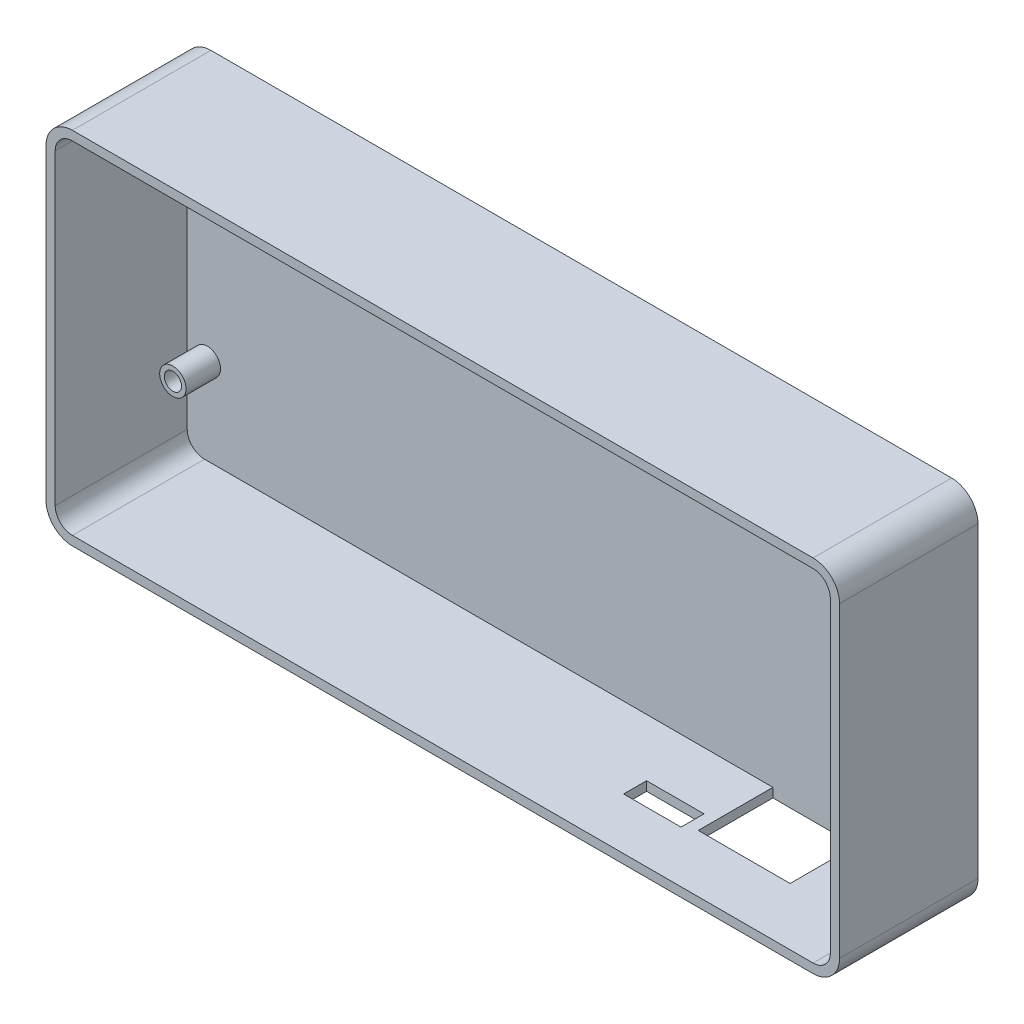
SolidWorks part; units mm, degrees
ref_plane "Alzado" through (0, 0, 0) normal (0, 0, 1) x (1, 0, 0)
ref_plane "Planta" through (0, 0, 0) normal (0, 1, 0) x (1, 0, 0)
ref_plane "Vista lateral" through (0, 0, 0) normal (1, 0, 0) x (0, 0, -1)
sketch "Croquis1" plane through (0, 0, 0) normal (0, 0, 1) x (1, 0, 0)
  line L0 (3, 61.1) -> (132, 61.1)
  line L1 (3, 0) -> (132, 0)
  line L2 (0, 3) -> (0, 56.5)
  line L3 (3, 59.5) -> (132, 59.5)
  line L4 (135, 3) -> (135, 56.5)
  line L5 (136.6, 3) -> (136.6, 56.5)
  line L6 (3, -1.6) -> (132, -1.6)
  line L7 (-1.6, 3) -> (-1.6, 56.5)
  arc A0 (132, 59.5) -> (135, 56.5) centre (132, 56.5) cw
  arc A1 (132, 0) -> (135, 3) centre (132, 3) ccw
  arc A2 (3, 0) -> (0, 3) centre (3, 3) cw
  arc A3 (0, 56.5) -> (3, 59.5) centre (3, 56.5) cw
  arc A4 (132, 61.1) -> (136.6, 56.5) centre (132, 56.5) cw
  arc A5 (132, -1.6) -> (136.6, 3) centre (132, 3) ccw
  arc A6 (3, -1.6) -> (-1.6, 3) centre (3, 3) cw
  arc A7 (-1.6, 56.5) -> (3, 61.1) centre (3, 56.5) cw
  point P9 (135, 0)
  point P12 (0, 0)
  point P15 (0, 59.5)
  dimension "D3" = 3
  dimension "D1" = 135
  dimension "D2" = 59.5
  dimension "D4" = 1.6
extrude "pared" add sketch "Croquis1" along normal blind 23
sketch "Croquis2" plane through (0, -1.6, 0) normal (0, -1, 0) x (1, 0, 0)
  line L0 (0, 23) -> (0, 0) construction
  line L1 (135, 23) -> (135, 0) construction
  line L2 (3, 23) -> (-1.6, 23) construction
  line L3 (-1.6, 23) -> (-1.6, 0) construction
  line L4 (-1.6, 0) -> (3, 0) construction
  line L5 (3, 0) -> (132, 0) construction
  line L6 (132, 0) -> (136.6, 0) construction
  line L7 (136.6, 23) -> (136.6, 0) construction
  line L8 (136.6, 23) -> (132, 23) construction
  line L9 (3, 23) -> (132, 23) construction
  line L10 (0, 23) -> (0, 0)
  line L11 (135, 23) -> (135, 0)
  line L12 (3, 23) -> (-1.6, 23)
  line L13 (-1.6, 23) -> (-1.6, 0)
  line L14 (-1.6, 0) -> (3, 0)
  line L15 (3, 0) -> (132, 0)
  line L16 (132, 0) -> (136.6, 0)
  line L17 (136.6, 23) -> (136.6, 0)
  line L18 (136.6, 23) -> (132, 23)
  line L19 (3, 23) -> (132, 23)
  line L21 (102, 13) -> (118, 13)
  line L22 (102, 13) -> (102, 0)
  line L23 (102, 0) -> (118, 0)
  line L24 (118, 13) -> (118, 0)
  line L25 (90, 14) -> (100, 14)
  line L26 (90, 14) -> (90, 10)
  line L27 (90, 10) -> (100, 10)
  line L28 (100, 14) -> (100, 10)
  dimension "D1" = 0
  dimension "D2" = 13
  dimension "D3" = 17
  dimension "D4" = 16
  dimension "D5" = 10
  dimension "D6" = 4
  dimension "D7" = 35
  dimension "D8" = 10
extrude "conectores" cut sketch "Croquis2" against normal up to next contours L24 L21 L22 L23 | L28 L25 L26 L27 region at (110, -1.6, 6.5) region at (95, -1.6, 12)
extrude "base frente" add sketch "Croquis1<2>" against normal blind 1.12 contours A6 L7 A7 L0 A4 L5 A5 L6
sketch "Croquis1<2>" plane through (0, 0, 0) normal (0, 0, 1) x (1, 0, 0) same geometry as "Croquis1"
sketch "Croquis3" plane through (0, 0, 0) normal (0, 0, 1) x (1, 0, 0)
  line L4 (135, 3) -> (135, 56.5)
  line L5 (132, 59.5) -> (3, 59.5)
  line L6 (0, 56.5) -> (0, 3)
  line L7 (3, 0) -> (102, 0)
  line L8 (135, 3) -> (135, 56.5)
  line L9 (132, 59.5) -> (3, 59.5)
  line L10 (0, 56.5) -> (0, 3)
  line L11 (3, 0) -> (102, 0)
  line L24 (130.5, 48) -> (130.5, 41.5) construction
  line L25 (130.5, 28.5) -> (130.5, 17.5) construction
  line L32 (102, 0) -> (102, -1.6)
  line L33 (102, 0) -> (102, -1.6)
  line L34 (102, -1.6) -> (118, -1.6)
  line L35 (102, -1.6) -> (118, -1.6)
  line L36 (118, -1.6) -> (118, 0)
  line L37 (118, -1.6) -> (118, 0)
  line L38 (118, 0) -> (132, 0)
  line L39 (118, 0) -> (132, 0)
  arc A4 (132, 0) -> (135, 3) centre (132, 3) ccw
  arc A5 (135, 56.5) -> (132, 59.5) centre (132, 56.5) ccw
  arc A6 (3, 59.5) -> (0, 56.5) centre (3, 56.5) ccw
  arc A7 (0, 3) -> (3, 0) centre (3, 3) ccw
  arc A8 (132, 0) -> (135, 3) centre (132, 3) ccw
  arc A9 (135, 56.5) -> (132, 59.5) centre (132, 56.5) ccw
  arc A10 (3, 59.5) -> (0, 56.5) centre (3, 56.5) ccw
  arc A11 (0, 3) -> (3, 0) centre (3, 3) ccw
  circle A16 centre (130.5, 48) radius 1.5
  circle A17 centre (130.5, 41.5) radius 1.5
  circle A18 centre (130.5, 35) radius 1.5
  circle A19 centre (130.5, 28.5) radius 1.5
  circle A20 centre (130.5, 17.5) radius 1.5
  circle A21 centre (130.5, 11.5) radius 2.5
  circle A22 centre (130.5, 48) radius 2.3
  circle A23 centre (130.5, 41.5) radius 2.3
  circle A24 centre (130.5, 35) radius 2.3
  circle A25 centre (130.5, 28.5) radius 2.3
  circle A26 centre (130.5, 17.5) radius 2.3
  circle A27 centre (130.5, 11.5) radius 3.3
  circle A28 centre (3.5, 15) radius 1.5
  circle A29 centre (3.5, 15) radius 2.3
  dimension "D8" = 0.8
  dimension "D14" = 3
  dimension "D3" = 5
  dimension "D6" = 3
  dimension "D2" = 6
  dimension "D4" = 0.8
  dimension "D5" = 4
  dimension "D7" = 131.5
  dimension "D12" = 6.5
  dimension "D13" = 11.5
  dimension "D15" = 4.5
  dimension "D17" = 11
  dimension "D9" = 15
  dimension "D1" = 0
  dimension "D16" = 2
extrude "luces" cut sketch "Croquis3" against normal up to next contours A16 | A17 | A18 | A19 | A20 | A21 | A28 region at (130.5, 48, 0) region at (130.5, 41.5, 0) region at (130.5, 35, 0) region at (130.5, 28.5, 0) region at (130.5, 17.5, 0) region at (130.5, 11.5, 0) region at (3.5, 15, 0)
extrude "Saliente-Extruir1" add sketch "Croquis3<3>" along normal blind 12 contours A26 A20 | A25 A19 | A24 A18 | A23 A17 | A22 A16 region at (128.2651, 48, 0) region at (128.2651, 41.5, 0) region at (128.2651, 35, 0) region at (128.2651, 28.5, 0) region at (128.2651, 17.5, 0)
sketch "Croquis3<3>" plane through (0, 0, 0) normal (0, 0, 1) x (1, 0, 0) same geometry as "Croquis3"
extrude "Saliente-Extruir2" add sketch "Croquis3<4>" along normal blind 9 contours A27 A21 region at (127.2933, 11.5, 0)
sketch "Croquis3<4>" plane through (0, 0, 0) normal (0, 0, 1) x (1, 0, 0) same geometry as "Croquis3"
extrude "Saliente-Extruir3" add sketch "Croquis3<5>" along normal blind 6 contours A29 A28 region at (1.2651, 15, 0)
sketch "Croquis3<5>" plane through (0, 0, 0) normal (0, 0, 1) x (1, 0, 0) same geometry as "Croquis3"
